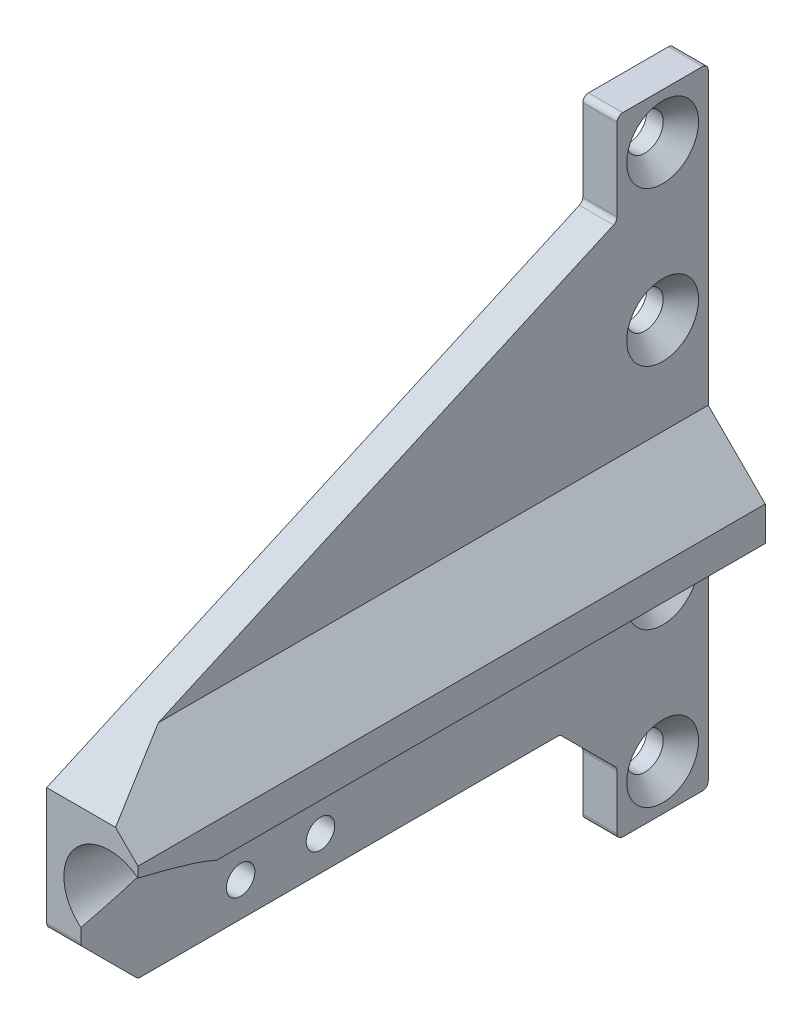
SolidWorks part; units mm, degrees
ref_plane "Front Plane" through (0, 0, 0) normal (0, 0, 1) x (1, 0, 0)
ref_plane "Top Plane" through (0, 0, 0) normal (0, 1, 0) x (1, 0, 0)
ref_plane "Right Plane" through (0, 0, 0) normal (1, 0, 0) x (0, 0, -1)
sketch "Sketch1" plane through (0, 0, 0) normal (0, 0, 1) x (1, 0, 0)
  line L0 (-736.1635, 0) -> (36072.0133, 0) construction
  line L1 (0, -736.1635) -> (0, 36072.0133) construction
  line L2 (25, 1.0355) -> (30, 1.0355) construction
  line L3 (0, 22) -> (22, 22) construction
  line L4 (0, 22) -> (0, -24.3053) construction
  line L5 (0, -24.3053) -> (22, -24.3053) construction
  line L6 (22, 22) -> (22, -24.3053) construction
  line L7 (22, -20) -> (25, -20)
  line L8 (22, -20) -> (22, 35)
  line L9 (22, 35) -> (25, 35)
  line L10 (25, -20) -> (25, 1.0355)
  line L11 (27.5, 3.5355) -> (25, 1.0355)
  line L12 (30, 1.0355) -> (30, 9.0355)
  line L13 (30, 9.0355) -> (25, 9.0355)
  line L14 (30, 1.0355) -> (27.5, 3.5355)
  line L15 (27.5, -3.5355) -> (29.2678, -1.7678) [skipped]
  line L16 (25, -1.0355) -> (25.7322, -1.7678) [skipped]
  line L17 (25, 9.0355) -> (25, 35)
  circle A0 centre (27.5, 0) radius 1.8404 construction
  circle A1 centre (27.5, 0) radius 2.5 construction
  dimension "D1" = 27.5
  dimension "D5" = 5
  dimension "D2" = 3
  dimension "D3" = 55
  dimension "D4" = 20
  dimension "D6" = 8
  dimension "D7" = 21.0355
extrude "Boss-Extrude1" add sketch "Sketch1" along normal blind 55
ref_axis "Axis1" through (27.5, 0, 0) along (0, 0, 1)
sketch "Sketch4" plane through (0, 0, 0) normal (0, 1, 0) x (1, 0, 0)
  line L0 (27.5, -47.0115) -> (30, -47.0115)
  line L1 (27.5, 0) -> (27.5, -76.1658) construction
  line L2 (30, -47.0115) -> (31.5, -55.0115)
  line L3 (31.5, -55.0115) -> (27.5, -55.0115)
  line L4 (27.5, -55.0115) -> (27.5, -47.0115)
  dimension "D1" = 4
  dimension "D2" = 2.5
  dimension "D3" = 8
revolve "Cut-Revolve1" cut sketch "Sketch4" angle 360 about axis through (27.5, 0, 0) along (0, 0, 1)
sketch "Sketch6" plane through (22, 0, 0) normal (-1, 0, 0) x (0, 0, 1)
  line L1 (55, 35) -> (0, 35) construction
  line L2 (55, 35) -> (55, -20) construction
  line L3 (55, 6) -> (55, 35)
  line L4 (55, 35) -> (8, 35)
  line L5 (0, -20) -> (0, 35) construction
  line L6 (0, 0) -> (76.1658, 0) construction
  line L7 (0, -20) -> (0, 1.0355) construction
  line L8 (55, -20) -> (8, -20)
  line L9 (55, -20) -> (55, -9.5)
  line L10 (55, -9.5) -> (8, -9.5)
  line L11 (8, -20) -> (8, -9.5)
  line L12 (8, 35) -> (8, 27)
  line L13 (8, 27) -> (55, 6)
  dimension "D1" = 8
  dimension "D2" = 6
  dimension "D3" = 9.5
  dimension "D4" = 8
  dimension "D5" = 8
extrude "Cut-Extrude3" cut sketch "Sketch6" against normal blind 55
chamfer "Chamfer3" distance 5 angle 45 2 edges at (23.5, -9.5, 8) (23.5, -9.5, 55)
chamfer "Chamfer4" distance 5 angle 45 1 edges at (30, 9.0355, 24.1031)
hole_wizard "CSK for M3 Flat Head Machine Screw1" positions "Sketch7" profile "Sketch8" countersink size "M3" standard "ANSI Metric" end condition through all
sketch "Sketch7" plane through (25, 0, 0) normal (1, 0, 0) x (0, 0, -1)
  line L0 (-8, 35) -> (0, 35) construction
  line L1 (0, -200736.1635) -> (0, 236072.0133) construction
  line L3 (-8, -20) -> (0, -20) construction
  point P0 (-4, 31)
  point P2 (-4, 17.5)
  point P4 (-4, -16)
  point P6 (-4, -2.5)
  dimension "D1" = 4
  dimension "D2" = 4
  dimension "D3" = 13.5
  dimension "D5" = 4
  dimension "D6" = 13.5
sketch "Sketch8" plane through (25, 31, 4) normal (0, 1, 0) x (0, 0, -1)
  line L0 (0, 0) -> (0, 3)
  line L1 (0, 3) -> (1.6, 3)
  line L2 (1.6, 3) -> (1.6, 1.55)
  line L3 (1.6, 1.55) -> (3.15, 0)
  line L5 (3.15, 0) -> (0, 0)
  line L6 (-1.6, 1.55) -> (-3.15, 0) construction
  line L11 (0, -6.35) -> (0, 107.95) construction
  dimension "Thru Hole Dia." = 3.2
  dimension "Thru Hole Depth" = 3
  dimension "Near C'Sink Dia." = 6.3
  dimension "Near C'Sink Angle" = 90
hole_wizard "Tap Drill for M3x0.5 Tap1" positions "Sketch9" profile "Sketch10" hole size "M3x0.5" standard "ANSI Metric" end condition through all
sketch "Sketch9" plane through (25, 0, 0) normal (1, 0, 0) x (0, 0, -1)
  line L0 (-55, -4.5) -> (-55, -3.1197) construction
  line L1 (-50, -9.5) -> (-13, -9.5) construction
  point P0 (-41, -6.5)
  point P2 (-34, -6.5)
  dimension "D1" = 7
  dimension "D2" = 14
  dimension "D3" = 3
sketch "Sketch10" plane through (25, -6.5, 41) normal (0, 1, 0) x (0, 0, -1)
  line L0 (0, 0) -> (0, 3)
  line L1 (0, 3) -> (1.25, 3)
  line L2 (1.25, 3) -> (1.25, 0)
  line L5 (1.25, 0) -> (0, 0)
  line L11 (0, -6.35) -> (0, 107.95) construction
  dimension "Thru Hole Dia." = 2.5
  dimension "Thru Hole Depth" = 3
fillet "Fillet1" radius 0.5 9 edges at (23.5, -4.5, 55) (23.5, -20, 0) (23.5, -9.5, 50) (23.5, -9.5, 13) (23.5, -14.5, 8) (23.5, -20, 8) (23.5, 35, 0) (23.5, 27, 8) (23.5, 35, 8)
